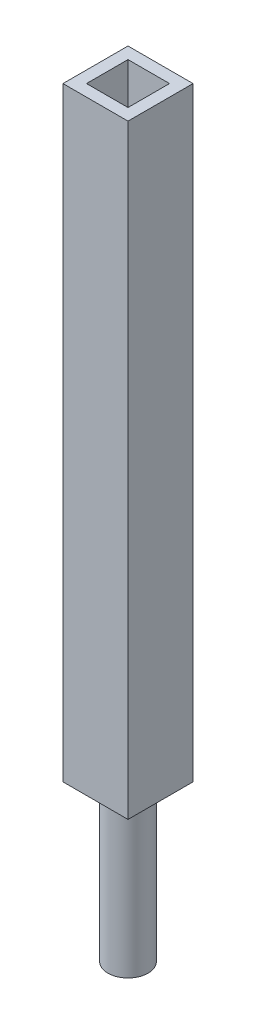
SolidWorks part; units mm, degrees
ref_plane "Front Plane" through (0, 0, 0) normal (0, 0, 1) x (1, 0, 0)
ref_plane "Top Plane" through (0, 0, 0) normal (0, 1, 0) x (1, 0, 0)
ref_plane "Right Plane" through (0, 0, 0) normal (1, 0, 0) x (0, 0, -1)
sketch "Sketch1" plane through (0, 0, 0) normal (0, 1, 0) x (1, 0, 0)
  line L1 (-5.969, 5.969) -> (5.969, 5.969)
  line L2 (-5.969, 5.969) -> (-5.969, -5.969)
  line L3 (-5.969, -5.969) -> (5.969, -5.969)
  line L4 (5.969, 5.969) -> (5.969, -5.969)
  line L9 (-5.969, 5.969) -> (5.969, -5.969) construction
  line L10 (-5.969, -5.969) -> (5.969, 5.969) construction
  point P0 (0, 0)
  dimension "D1" = 11.938
  dimension "D2" = 11.938
extrude "Boss-Extrude1" add sketch "Sketch1" along normal blind 213.106
sketch "Sketch2" plane through (0, 213.106, 0) normal (0, 1, 0) x (1, 0, 0)
  circle A0 centre (0, 0) radius 3.6805
  dimension "D1" = 7.3609
extrude "Boss-Extrude2" add sketch "Sketch2" along normal blind 22.225
sketch "Sketch3" plane through (0, 0, 0) normal (0, -1, 0) x (-1, 0, 0)
  circle A0 centre (0, 0) radius 3.6805
  dimension "D1" = 7.3609
extrude "Boss-Extrude3" add sketch "Sketch3" along normal blind 28.575
sketch "Sketch4" plane through (0, 235.331, 0) normal (0, 1, 0) x (1, 0, 0)
  line L1 (-2.286, 2.286) -> (2.286, 2.286)
  line L2 (-2.286, 2.286) -> (-2.286, -2.286)
  line L3 (-2.286, -2.286) -> (2.286, -2.286)
  line L4 (2.286, 2.286) -> (2.286, -2.286)
  line L5 (-2.286, 2.286) -> (2.286, -2.286) construction
  line L6 (-2.286, -2.286) -> (2.286, 2.286) construction
  point P0 (0, 0)
  dimension "D1" = 4.572
  dimension "D2" = 4.572
extrude "Boss-Extrude4" add sketch "Sketch4" along normal blind 15.24
sketch "Sketch5" plane through (0, 250.571, 0) normal (0, 1, 0) x (1, 0, 0)
  circle A0 centre (0, 0) radius 13.0511
extrude "Cut-Extrude1" cut sketch "Sketch5" against normal blind 139.573
sketch "Sketch6" plane through (0, 110.998, 0) normal (0, 1, 0) x (1, 0, 0)
  line L1 (-3.81, -3.81) -> (3.81, -3.81)
  line L2 (-3.81, -3.81) -> (-3.81, 3.81)
  line L3 (-3.81, 3.81) -> (3.81, 3.81)
  line L4 (3.81, -3.81) -> (3.81, 3.81)
  line L5 (-3.81, -3.81) -> (3.81, 3.81) construction
  line L6 (-3.81, 3.81) -> (3.81, -3.81) construction
  point P0 (0, 0)
  dimension "D1" = 7.62
  dimension "D2" = 7.62
extrude "Cut-Extrude2" cut sketch "Sketch6" against normal blind 12.7
